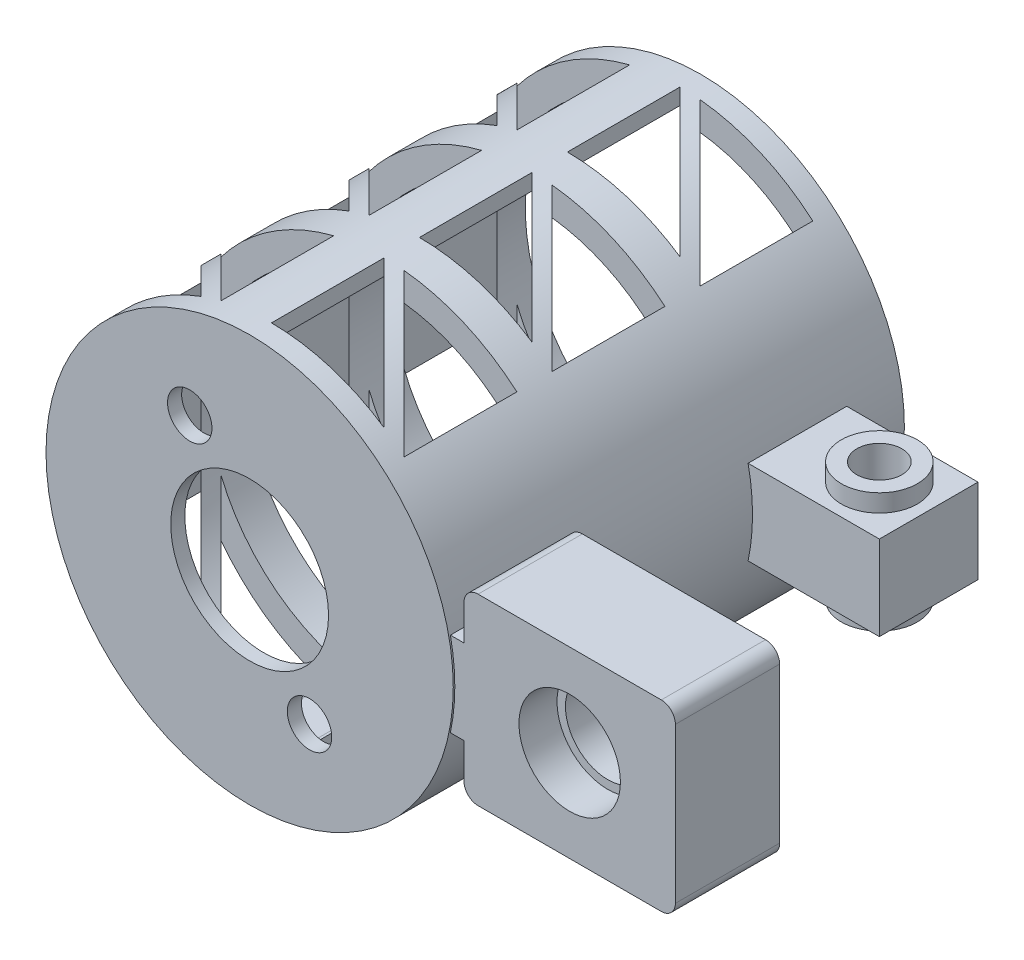
SolidWorks part; units mm, degrees
material "HighTemp SLA"
ref_plane "Plan de face" through (0, 0, 0) normal (0, 0, 1) x (1, 0, 0)
ref_plane "Plan de dessus" through (0, 0, 0) normal (0, 1, 0) x (1, 0, 0)
ref_plane "Plan de droite" through (0, 0, 0) normal (1, 0, 0) x (0, 0, -1)
sketch "Esquisse1" plane through (0, 0, 0) normal (0, 0, 1) x (1, 0, 0)
  circle A0 centre (0, 0) radius 12.45
  circle A1 centre (0, 0) radius 14.45
  dimension "D1" = 24.9
  dimension "D2" = 2
extrude "Boss.-Extru.1" add sketch "Esquisse1" along normal blind 31.01
sketch "Esquisse2" plane through (0, 0, 31.01) normal (0, 0, 1) x (1, 0, 0)
  circle A0 centre (0, 0) radius 14.45
  circle A1 centre (0, 0) radius 5.6
  circle A3 centre (0, 0) radius 14.45 construction
  circle M1 centre (0, 0) radius 14.45
  circle M2 centre (0, 0) radius 12.45
  dimension "D1" = 11.2
extrude "Boss.-Extru.2" add sketch "Esquisse2" along normal blind 1 contours A1 M2 | M1 M2 region at (-14.0413, 0, 31.01) region at (-12.0979, 0, 31.01)
sketch "Esquisse7" plane through (0, 0, 0) normal (0, 1, 0) x (1, 0, 0)
  line L0 (22.6, -31.9) -> (22.6, -24.5) construction
  line L5 (15.1, -24.5) -> (15.1, -31.9) construction
  line L6 (15.1, -24.5) -> (30.1, -24.5)
  line L7 (15.1, -31.9) -> (30.1, -31.9)
  line L8 (30.1, -24.5) -> (30.1, -31.9)
  line L10 (0, -28.2) -> (7.4, -28.2) construction
  line L11 (0, -28.2) -> (0, 0) construction
  line L12 (14.45, 0) -> (-14.45, 0) construction
  line L15 (15.1, -31.9) -> (13.63, -31.9)
  line L16 (13.63, -31.9) -> (13.63, -24.5)
  line L17 (13.63, -24.5) -> (15.1, -24.5)
  line L18 (22.6, -28.2) -> (7.4, -28.2) construction
  dimension "D4" = 7.4
  dimension "D5" = 15.2
  dimension "D1" = 7.4
  dimension "D2" = 24.5
  dimension "D3" = 15
  dimension "D6" = 15.1
extrude "Boss.-Extru.6" add sketch "Esquisse7" along normal blind 3 and the other way blind 3 contours L6 L8 L7 L15 L16 L17
sketch "Esquisse8" plane through (0, 3, 0) normal (0, 1, 0) x (1, 0, 0)
  line L0 (30.1, -31.9) -> (30.1, -24.5)
  line L1 (30.1, -31.9) -> (15.1, -31.9)
  line L2 (30.1, -24.5) -> (15.1, -24.5)
  line L3 (15.1, -31.9) -> (15.1, -24.5)
  dimension "D1" = 15
extrude "Boss.-Extru.7" add sketch "Esquisse8" along normal blind 3.5
mirror "Symétrie1" about plane through (0, 0, 0) normal (0, 1, 0) of "Boss.-Extru.7"
sketch "Esquisse9" plane through (0, 0, 24.5) normal (0, 0, -1) x (-1, 0, 0)
  line L0 (-30.1, 6.5) -> (-15.1, -6.5) construction
  line L1 (-15.1, 6.5) -> (-30.1, -6.5) construction
  circle A0 centre (-22.6, 0) radius 3.6
  dimension "D1" = 7.2
extrude "Enlèv. mat.-Extru.2" cut sketch "Esquisse9" against normal blind 2.7
sketch "Esquisse10" plane through (0, 0, 31.9) normal (0, 0, 1) x (1, 0, 0)
  line L0 (15.1, 6.5) -> (30.1, -6.5) construction
  line L1 (15.1, -6.5) -> (30.1, 6.5) construction
  circle A0 centre (22.6, 0) radius 3.6
  dimension "D1" = 7.2
extrude "Enlèv. mat.-Extru.3" cut sketch "Esquisse10" against normal blind 2.7
sketch "Esquisse11" plane through (0, 0, 27.2) normal (0, 0, -1) x (-1, 0, 0)
  circle A0 centre (-22.6, 0) radius 3
  dimension "D1" = 6
extrude "Enlèv. mat.-Extru.4" cut sketch "Esquisse11" against normal through all contours A0
fillet "Congé2" radius 1 4 edges at (15.1, -6.5, 28.2) (15.1, 6.5, 28.2) (30.1, -6.5, 28.2) (30.1, 6.5, 28.2)
sketch "Esquisse12" plane through (0, 0, 24.5) normal (0, 0, -1) x (-1, 0, 0)
  line L0 (-16.1, 6.5) -> (-16.1, -6.5) construction
  line L5 (-29.1, 6.5) -> (-29.1, -6.5) construction
  line L6 (-29.1, 6.5) -> (-16.1, 6.5) construction
  line L11 (-29.1, 6.5) -> (-16.1, -6.5) construction
  line L12 (-16.1, 6.5) -> (-29.1, -6.5) construction
  arc A4 (-29.1, 6.5) -> (-30.1, 5.5) centre (-29.1, 5.5) ccw construction
  circle A5 centre (-27.6858, 5.0858) radius 0.8
  circle A6 centre (-17.5142, -5.0858) radius 0.8
  circle A7 centre (-17.5142, 5.0858) radius 0.8
  circle A8 centre (-27.6848, -5.0848) radius 0.8
  dimension "D4" = 2
  dimension "D5" = 2.0014
  dimension "D3" = 2
  dimension "D1" = 1.6
  dimension "D2" = 2
extrude "Enlèv. mat.-Extru.5" [suppressed] cut sketch "Esquisse12" against normal blind 10
sketch "Esquisse13" plane through (0, 0, 0) normal (0, 1, 0) x (1, 0, 0)
  line L0 (14.45, -24.5) -> (14.45, 0) construction
  line L1 (23.45, -3.7764) -> (13.45, -3.7764)
  line L2 (23.45, -3.7764) -> (23.45, -10.7764)
  line L3 (23.45, -10.7764) -> (13.45, -10.7764)
  line L4 (13.45, -3.7764) -> (13.45, -10.7764)
  line L5 (23.45, -3.7764) -> (13.45, -10.7764) construction
  line L6 (23.45, -10.7764) -> (13.45, -3.7764) construction
  point P0 (18.45, -7.2764)
  dimension "D1" = 1
  dimension "D2" = 10
  dimension "D3" = 7
extrude "Boss.-Extru.8" add sketch "Esquisse13" along normal blind 3 and the other way blind 3
sketch "Esquisse14" plane through (0, -3, 0) normal (0, -1, 0) x (1, 0, 0)
  line L0 (23.45, 3.7764) -> (16.45, 10.7764) construction
  line L1 (14.1352, 10.7764) -> (23.45, 10.7764) construction
  circle A0 centre (19.95, 7.2764) radius 1.6
  dimension "D1" = 3.2
  dimension "D2" = 7
extrude "Enlèv. mat.-Extru.6" cut sketch "Esquisse14" against normal through all
sketch "Esquisse15" plane through (0, -3, 0) normal (0, -1, 0) x (1, 0, 0)
  circle A0 centre (19.95, 7.2764) radius 2.7
  circle A1 centre (19.95, 7.2764) radius 1.5
  circle M1 centre (19.95, 7.2764) radius 1.6
  dimension "D1" = 1.2
extrude "Boss.-Extru.9" add sketch "Esquisse15" along normal blind 1.25 contours A0 M1 region at (17.3264, -3, 7.2764)
mirror "Symétrie2" about plane through (0, 0, 0) normal (0, 1, 0) of "Boss.-Extru.9"
sketch "Esquisse16" plane through (0, 0, 32.01) normal (0, 0, 1) x (1, 0, 0)
  line L0 (0, 14.45) -> (0, -14.45) construction
  line L1 (0, 0) -> (7.225, -12.5141) construction
  circle A0 centre (0, 0) radius 14.45 construction
  circle A1 centre (4.25, -7.3612) radius 1.575
  dimension "D2" = 3.15
  dimension "D1" = 30
  dimension "D3" = 8.5
extrude "Enlèv. mat.-Extru.7" cut sketch "Esquisse16" against normal blind 10 contours A1
pattern_circular "Répétition circulaire2" count 2 over 360 about axis through (0, 0, 32.01) along (0, 0, 1) of "Enlèv. mat.-Extru.7"
sketch "Esquisse17" plane through (0, 0, 0) normal (0, 1, 0) x (1, 0, 0)
  line L0 (-12.95, -30.51) -> (-12.95, -22.51)
  line L1 (-12.95, -22.51) -> (-4.95, -30.51)
  line L2 (-4.95, -30.51) -> (-12.95, -30.51)
  line L3 (-11.5358, -22.51) -> (-3.5358, -30.51)
  line L4 (-3.5358, -30.51) -> (-3.5358, -22.51)
  line L5 (-3.5358, -22.51) -> (-11.5358, -22.51)
  line L7 (-14.45, 0) -> (-14.45, -32.01) construction
  line L8 (-14.45, -32.01) -> (14.45, -32.01) construction
  dimension "D1" = 1
  dimension "D2" = 8
  dimension "D3" = 8
  dimension "D4" = 1.5
  dimension "D5" = 1.5
extrude "Enlèv. mat.-Extru.8" cut sketch "Esquisse17" against normal through all and the other way through all
pattern_linear "Répétition linéaire1" count 3 spacing 10.5 along (0, 0, -1) of "Enlèv. mat.-Extru.8"
pattern_linear "Répétition linéaire2" count 2 spacing 13 along (1, 0, 0) of "Répétition linéaire1"
sketch "Esquisse18" plane through (0, 0, 0) normal (0, 0, -1) x (-1, 0, 0)
  line L0 (0.1717, -12.3373) -> (3.1717, -12.3373) construction
  line L1 (0.1717, -11.7373) -> (3.1717, -11.7373)
  line L2 (0.1717, -12.9373) -> (3.1717, -12.9373)
  circle A1 centre (0, 0) radius 12.45 construction
  arc A2 (0.1717, -11.7373) -> (0.1717, -12.9373) centre (0.1717, -12.3373) ccw
  arc A3 (3.1717, -12.9373) -> (3.1717, -11.7373) centre (3.1717, -12.3373) ccw
  circle A4 centre (0, 0) radius 12.45 construction
  point P6 (1.6717, -12.3373)
  dimension "D1" = 1.2
  dimension "D2" = 3
extrude "Enlèv. mat.-Extru.9" cut sketch "Esquisse18" against normal up to surface (31.01 mm away) up to face at (-2.675, 7.3612, 31.01)
pattern_circular "Répétition circulaire3" count 4 every 65 about axis through (0, 0, 0) along (0, 0, 1) of "Enlèv. mat.-Extru.9"
